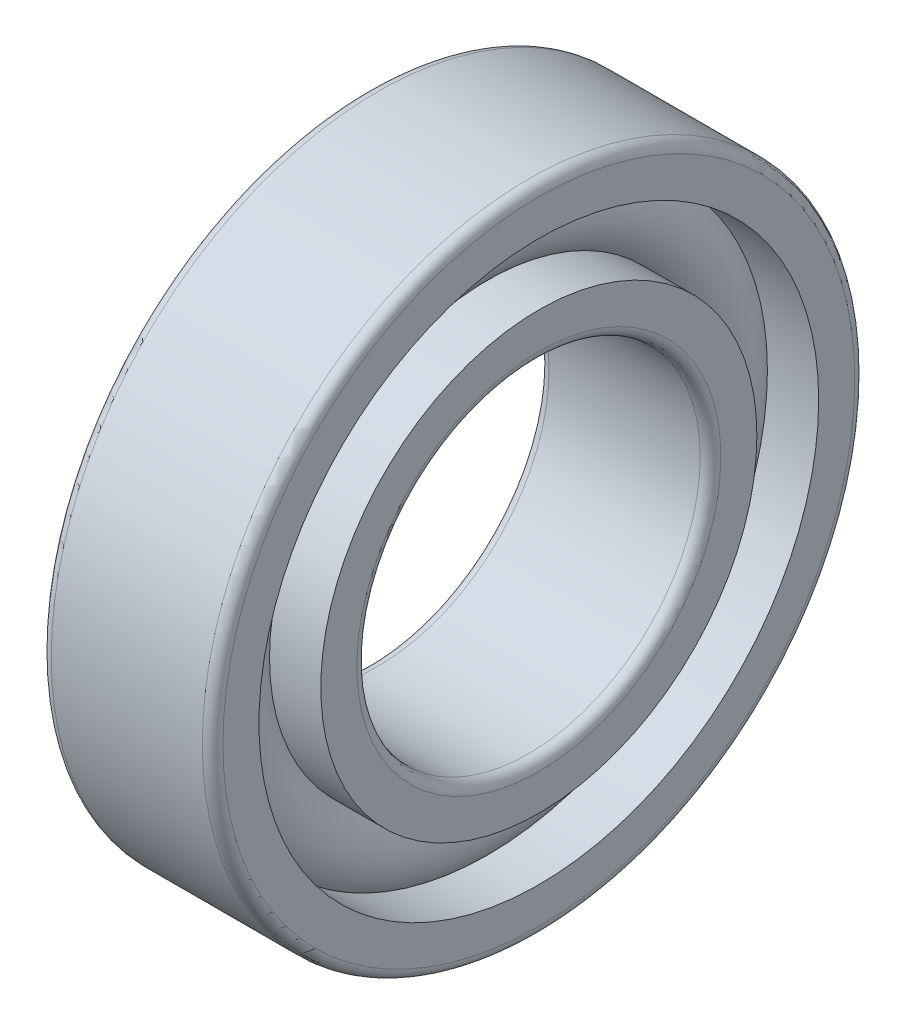
SolidWorks part; units mm, degrees
ref_plane "Plane1" through (0, 0, 0) normal (0, 0, 1) x (1, 0, 0)
ref_plane "Plane2" through (0, 0, 0) normal (0, 1, 0) x (1, 0, 0)
ref_plane "Plane3" through (0, 0, 0) normal (1, 0, 0) x (0, 0, -1)
sketch "Clipboard" plane through (0, 0, 0) normal (0, 0, 1) x (1, 0, 0)
  line L0 (-10, 0) -> (10, 0) construction
  line L1 (0, 0) -> (22.3471, -0.7804)
  line L2 (0, 0) -> (7.2456, 0.253)
  line L3 (0, 0) -> (22.3471, -0.7804)
  line L4 (0, 0) -> (-22.3573, -0.3902)
  dimension "BallCLRad" = 7.25
sketch "CagSpiSke" plane through (0, 0, 0) normal (0, 0, 1) x (1, 0, 0)
  line L0 (0.135, 7.025) -> (0.135, 7.475)
  line L1 (0.135, 7.475) -> (-0.135, 7.475)
  line L2 (-0.135, 7.475) -> (-0.135, 7.025)
  line L3 (-0.135, 7.025) -> (0.135, 7.025)
  line L4 (-20.6375, 0) -> (20.6375, 0) construction
  line L5 (0, 0) -> (0, 23.7692) construction
  dimension "OD" = 14.95
  dimension "ID" = 14.05
revolve "CageSpine" add sketch "CagSpiSke" angle 0.001 about L4 reverse direction yes
ref_axis "Axis1" through (-50, 0, 0) along (1, 0, 0)
sketch "CagBalSke" plane through (0, 0, 0) normal (0, 0, 1) x (1, 0, 0)
  line L0 (-1.485, 7.25) -> (1.485, 7.25)
  line L1 (-1.905, 7.25) -> (1.905, 7.25) construction
  line L2 (-10, 0) -> (10, 0) construction
  line L3 (0, 0) -> (0, 24) construction
  arc A0 (1.485, 7.25) -> (-1.485, 7.25) centre (0, 7.25) cw
  dimension "BallCLRad" = 7.25
revolve "CageBall" [suppressed] add sketch "CagBalSke" angle 360 about L1 reverse direction yes
pattern_circular "CageBalls" [suppressed] count 2 every 180 about axis through (-50, 0, 0) along (1, 0, 0)
sketch "CagTrmODSke" plane through (0, 0, 0) normal (0, 0, 1) x (1, 0, 0)
  line L0 (1.486, 7.475) -> (1.486, 8.736)
  line L1 (1.486, 8.736) -> (-1.486, 8.736)
  line L2 (-1.486, 8.736) -> (-1.486, 7.475)
  line L3 (-1.486, 7.475) -> (1.486, 7.475)
  line L4 (-20.6375, 0) -> (20.6375, 0) construction
  line L5 (0, 0) -> (0, 25) construction
  dimension "Width" = 2.972
  dimension "ID" = 14.95
  dimension "OD" = 17.472
revolve "CageTrimOD" [suppressed] cut sketch "CagTrmODSke" angle 360 about L4 reverse direction yes
sketch "CagTrmIDSke" plane through (0, 0, 0) normal (0, 0, 1) x (1, 0, 0)
  line L0 (1.486, 5.766) -> (1.486, 7.025)
  line L1 (1.486, 7.025) -> (-1.486, 7.025)
  line L2 (-1.486, 7.025) -> (-1.486, 5.766)
  line L3 (-1.486, 5.766) -> (1.486, 5.766)
  line L4 (-20.6375, 0) -> (20.6375, 0) construction
  line L5 (0, 0) -> (0, 25) construction
  dimension "Width" = 2.972
  dimension "ID" = 11.532
  dimension "OD" = 14.05
revolve "CageTrimID" [suppressed] cut sketch "CagTrmIDSke" angle 360 about L4 reverse direction yes
sketch "BalSimSke" plane through (0, 0, 0) normal (0, 0, 1) x (1, 0, 0)
  line L0 (-10, 0) -> (10, 0) construction
  line L1 (-10, 7.25) -> (10, 7.25) construction
  line L2 (0, 0) -> (0, 23) construction
  circle A0 centre (0, 7.25) radius 1.35
  dimension "BallCLRad" = 7.25
  dimension "Ball_diameter" = 2.7
revolve "BallsSimplified" add sketch "BalSimSke" angle 360 about L0
sketch "BalDetSke" plane through (0, 0, 0) normal (0, 0, 1) x (1, 0, 0)
  line L0 (-1.35, 7.25) -> (1.35, 7.25)
  line L1 (-1.905, 7.25) -> (1.905, 7.25) construction
  line L2 (0, 0) -> (0, 25) construction
  arc A0 (1.35, 7.25) -> (-1.35, 7.25) centre (0, 7.25) cw
  dimension "BallCLRad" = 7.25
  dimension "Ball_diameter" = 2.7
revolve "BallDetailed" [suppressed] add sketch "BalDetSke" angle 360 about L1 reverse direction yes
sketch "InnRacSke" plane through (0, 0, 0) normal (0, 0, 1) x (1, 0, 0)
  line L0 (-0.9724, 6.35) -> (-2.5, 6.35)
  line L1 (-2.5, 6.35) -> (-2.5, 5.3)
  line L2 (-2.2, 5) -> (2.2, 5)
  line L3 (2.5, 5.3) -> (2.5, 6.35)
  line L4 (2.5, 6.35) -> (0.9724, 6.35)
  line L5 (-20.6375, 0) -> (20.6375, 0) construction
  line L6 (0, 0) -> (0, 30) construction
  arc A0 (-2.5, 5.3) -> (-2.2, 5) centre (-2.2, 5.3) ccw
  arc A1 (2.2, 5) -> (2.5, 5.3) centre (2.2, 5.3) ccw
  arc A2 (0.9724, 6.35) -> (-0.9724, 6.35) centre (0, 7.25) cw
  dimension "BallCLRad" = 7.25
  dimension "Fillet_radius" = 0.3
  dimension "Ball_diameter" = 2.65
  dimension "ID" = 10
  dimension "OD" = 12.7
  dimension "Width" = 5
revolve "InnerRace" add sketch "InnRacSke" angle 360 about L5 reverse direction yes
sketch "OutRacSke" plane through (0, 0, 0) normal (0, 0, 1) x (1, 0, 0)
  line L0 (-0.9724, 8.15) -> (-2.5, 8.15)
  line L1 (-2.5, 8.15) -> (-2.5, 9.2)
  line L2 (-2.2, 9.5) -> (2.2, 9.5)
  line L3 (2.5, 9.2) -> (2.5, 8.15)
  line L4 (2.5, 8.15) -> (0.9724, 8.15)
  line L5 (-20.6375, 0) -> (20.6375, 0) construction
  line L6 (0, 0) -> (0, 30) construction
  arc A0 (-2.5, 9.2) -> (-2.2, 9.5) centre (-2.2, 9.2) cw
  arc A1 (2.2, 9.5) -> (2.5, 9.2) centre (2.2, 9.2) cw
  arc A2 (0.9724, 8.15) -> (-0.9724, 8.15) centre (0, 7.25) ccw
  dimension "BallCLRad" = 7.25
  dimension "Fillet_radius" = 0.3
  dimension "Ball_diameter" = 2.65
  dimension "Width" = 5
revolve "OuterRace" add sketch "OutRacSke" angle 360 about L5 reverse direction yes
pattern_circular "BallsDetailed" [suppressed] count 2 every 180 about axis through (-50, 0, 0) along (1, 0, 0)
equation "\"BallCLRad@Clipboard\" = ( \"OD@OutRacSke\" + \"ID@InnRacSke\" ) / 4"
equation "\"BallCLRad@BalSimSke\" = \"BallCLRad@Clipboard\""
equation "\"BallCLRad@BalDetSke\" = \"BallCLRad@Clipboard\""
equation "\"BallCLRad@InnRacSke\" = \"BallCLRad@Clipboard\""
equation "\"BallCLRad@OutRacSke\" = \"BallCLRad@Clipboard\""
equation "\"Ball_diameter@InnRacSke\" = \"Ball_diameter@BalDetSke\" - 0.05"
equation "\"Ball_diameter@OutRacSke\" = \"Ball_diameter@BalDetSke\" - 0.05"
equation "\"Ball_diameter@BalSimSke\" = \"Ball_diameter@BalDetSke\""
equation "\"Width@OutRacSke\" = \"Width@InnRacSke\""
equation "\"Fillet_radius@OutRacSke\" = \"Fillet_radius@InnRacSke\""
equation "\"Max_count@Clipboard\" = int( 3.14159265 / atn(( \"Ball_diameter@BalDetSke\" / 2) / sqr( \"BallCLRad@Clipboard\"  *  \"BallCLRad@Clipboard\" - ( \"Ball_diameter@BalDetSke\" / 2) *  ( \"Ball_diameter@BalDetSke\" / 2))))"
equation "\"Max_count@Clipboard\" = ((sgn( \"Max_count@Clipboard\" - \"Count@Clipboard\" )-1)*( \"Max_count@Clipboard\" - \"Count@Clipboard\" ))/-2+ \"Count@Clipboard\""
equation "\"Count@BallsDetailed\" = int( \"Show_count@Clipboard\" ) "
equation "\"Count@BallsDetailed\" = ((sgn( \"Count@BallsDetailed\" - \"Max_count@Clipboard\" )-1)*( \"Count@BallsDetailed\" - \"Max_count@Clipboard\" ))/-2+ \"Max_count@Clipboard\""
equation "\"Count@BallsDetailed\" = ((sgn( \"Count@BallsDetailed\" - \"Min_count@Clipboard\" )+1)*( \"Count@BallsDetailed\" - \"Min_count@Clipboard\"))/2 +\"Min_count@Clipboard\""
equation "\"Angle@BallsDetailed\" = 360.0 / \"Max_count@Clipboard\""
equation "\"BallCLRad@CagBalSke\" = \"BallCLRad@Clipboard\""
equation "\"Count@CageBalls\" = \"Count@BallsDetailed\""
equation "\"Angle@CageBalls\" = \"Angle@BallsDetailed\""
equation "\"Angle@CageSpine\" =  \"Angle@CageBalls\" * ( \"Count@CageBalls\" -1 + int( \"Count@CageBalls\" / \"Max_count@Clipboard\" ) )  + 0.001 -  int( \"Count@CageBalls\" / \"Max_count@Clipboard\" ) * 0.001"
equation "\"Angle@CageSpine\" =  \"Angle@CageSpine\" * int( \"Min_count@Clipboard\" / 2) + int(1 / \"Min_count@Clipboard\")  * 0.001"
equation "\"CageWallOD@CagBalSke\" =  \"Ball_diameter@BalDetSke\" * 1.1"
equation "\"Thickness@CagSpiSke\" =  \"Ball_diameter@BalDetSke\" * 0.1"
equation "\"OD@CagTrmODSke\" = \"BallCLRad@Clipboard\" * 2 + \"CageWallOD@CagBalSke\" + 0.002"
equation "\"ID@CagTrmODSke\" = \"BallCLRad@Clipboard\" * 2 + \"Ball_diameter@BalDetSke\" / 6"
equation "\"OD@CagTrmIDSke\" = \"BallCLRad@Clipboard\" * 2 - \"Ball_diameter@BalDetSke\" / 6"
equation "\"ID@CagTrmIDSke\" = \"BallCLRad@Clipboard\" * 2 - \"CageWallOD@CagBalSke\" + 0.002"
equation "\"OD@CagSpiSke\" = \"ID@CagTrmODSke\""
equation "\"ID@CagSpiSke\" = \"OD@CagTrmIDSke\""
equation "\"Width@CagTrmODSke\" = \"CageWallOD@CagBalSke\" + 0.002"
equation "\"Width@CagTrmIDSke\" = \"CageWallOD@CagBalSke\" + 0.002"
